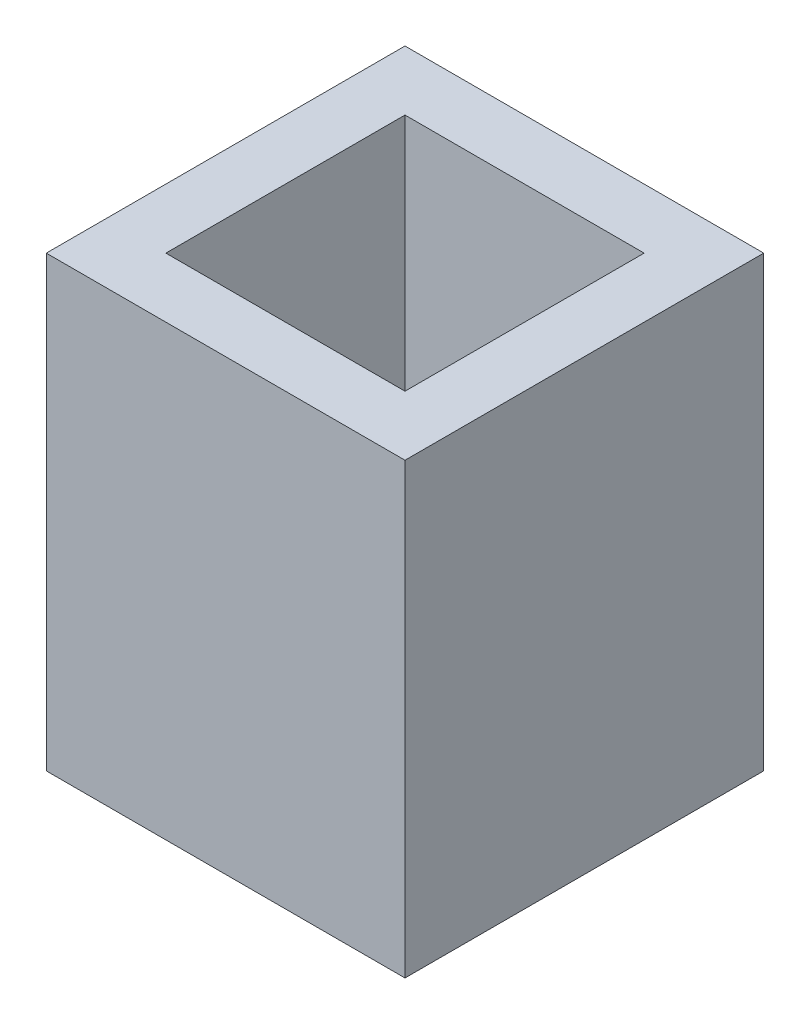
SolidWorks part; units mm, degrees
ref_plane "前视基准面" through (0, 0, 0) normal (0, 0, 1) x (1, 0, 0)
ref_plane "上视基准面" through (0, 0, 0) normal (0, 1, 0) x (1, 0, 0)
ref_plane "右视基准面" through (0, 0, 0) normal (1, 0, 0) x (0, 0, -1)
sketch "草图1" plane through (0, 0, 0) normal (0, 1, 0) x (1, 0, 0)
  line L0 (0, 0) -> (0, 24)
  line L1 (0, 0) -> (24, 0)
  line L2 (0, 24) -> (24, 24)
  line L3 (24, 0) -> (24, 24)
  line L4 (0, 0) -> (0, 20)
  line L5 (0, 0) -> (20, 0)
  line L6 (4, 20) -> (20, 20)
  line L7 (20, 4) -> (20, 20)
  line L8 (20, 20) -> (4, 20)
  line L9 (20, 20) -> (20, 4)
  line L10 (4, 20) -> (4, 4)
  line L11 (20, 4) -> (4, 4)
  point P3 (0, 0)
extrude "凸台-拉伸1" add sketch "草图1" along normal blind 30 contours L1 L3 L2 L0 L7 L11 L10 L6 region at (0.3394, 0, -10)
sketch "草图2" plane through (0, 0, 0) normal (0, 0, 1) x (1, 0, 0)
  line L0 (12, 0) -> (12, 15)
  line L1 (0, 0) -> (24, 0) construction
